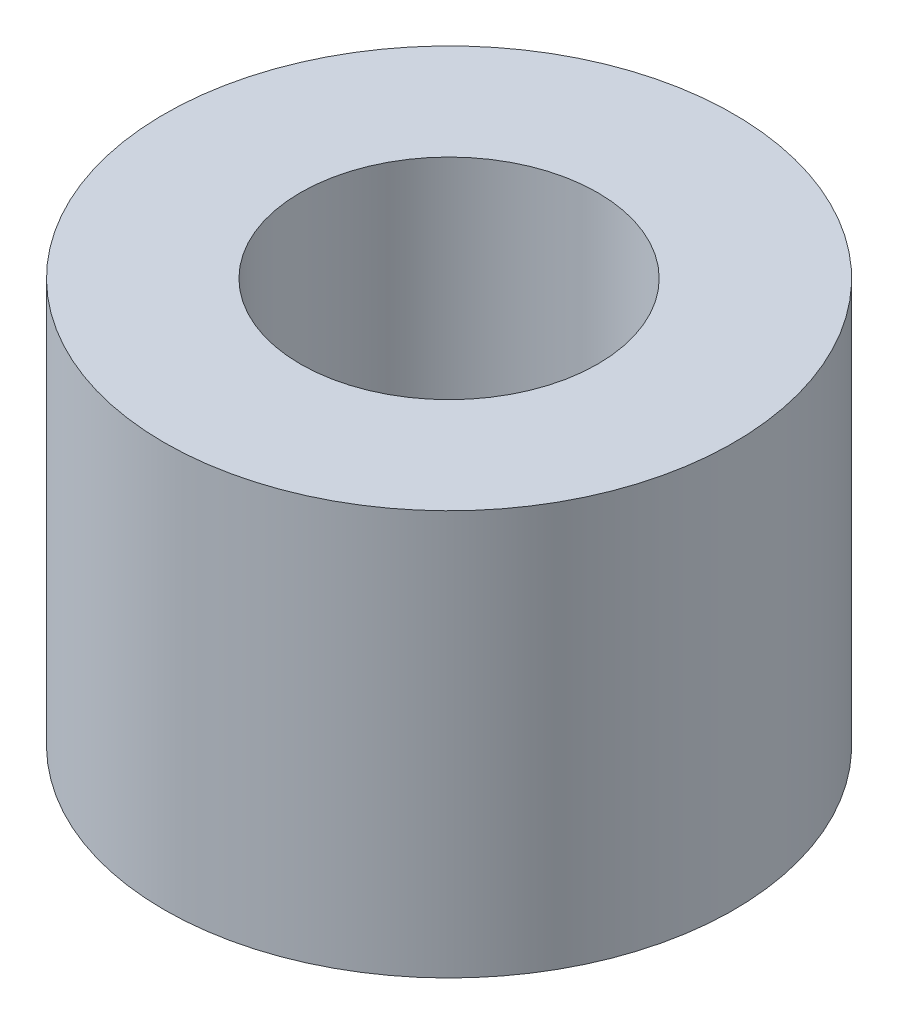
SolidWorks part; units mm, degrees
ref_plane "Front Plane" through (0, 0, 0) normal (0, 0, 1) x (1, 0, 0)
ref_plane "Top Plane" through (0, 0, 0) normal (0, 1, 0) x (1, 0, 0)
ref_plane "Right Plane" through (0, 0, 0) normal (1, 0, 0) x (0, 0, -1)
sketch "Sketch1" plane through (0, 0, 0) normal (0, 1, 0) x (1, 0, 0)
  circle A0 centre (0, 0) radius 2.075
  circle A1 centre (0, 0) radius 3.975
  dimension "D1" = 7.95
  dimension "D2" = 4.15
extrude "Boss-Extrude1" add sketch "Sketch1" along normal blind 5.65
